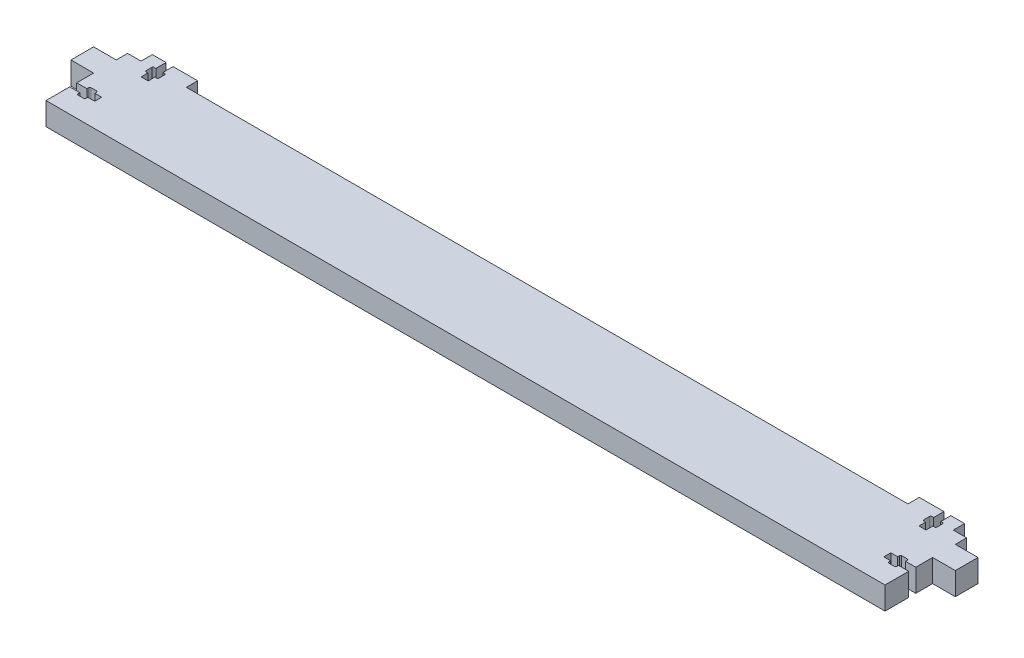
SolidWorks part; units mm, degrees
ref_plane "Front Plane" through (0, 0, 0) normal (0, 0, 1) x (1, 0, 0)
ref_plane "Top Plane" through (0, 0, 0) normal (0, 1, 0) x (1, 0, 0)
ref_plane "Right Plane" through (0, 0, 0) normal (1, 0, 0) x (0, 0, -1)
sketch "Sketch1" plane through (0, 0, 0) normal (0, 1, 0) x (1, 0, 0)
  line L0 (0, 18) -> (0, -18) construction
  line L1 (-185, 18) -> (0, 18)
  line L2 (-185, 18) -> (-185, 13)
  line L3 (-185, -18) -> (0, -18)
  line L4 (0, 18) -> (0, -18)
  line L5 (-185, 18) -> (0, 0) construction
  line L6 (-185, -18) -> (0, 0) construction
  line L7 (-185, 13) -> (-195, 13)
  line L8 (-195, 13) -> (-195, 3)
  line L9 (-195, 3) -> (-185, 3)
  line L10 (-185, 3) -> (-185, -18)
  point P0 (0, 0)
  dimension "D6" = 10
  dimension "D7" = 10
  dimension "D1" = 185
  dimension "D2" = 36
  dimension "D4" = 5
  dimension "D9" = 18
extrude "MainShape" add sketch "Sketch1" along normal blind 10 contours L2 L7 L8 L9 region at (-93.9423, 0, -0.1183)
sketch "Sketch15" plane through (0, 10, 0) normal (0, 1, 0) x (1, 0, 0)
  line L0 (-185, 18) -> (0, 18) construction
  line L1 (-159.1, 23) -> (-179.1, 23)
  line L2 (-159.1, 23) -> (-159.1, 13)
  line L3 (-159.1, 13) -> (-179.1, 13)
  line L4 (-179.1, 23) -> (-179.1, 13)
  line L5 (-159.1, 23) -> (-179.1, 13) construction
  line L6 (-159.1, 13) -> (-179.1, 23) construction
  line L7 (-185, 18) -> (-185, 13) construction
  point P0 (-169.1, 18)
  dimension "D1" = 20
  dimension "D2" = 5
  dimension "D3" = 15.9
extrude "Boss-Extrude4" add sketch "Sketch15" against normal through all
sketch "Sketch2" plane through (0, 10, 0) normal (0, 1, 0) x (1, 0, 0)
  line L0 (-171.5, 23) -> (-171.5, 12) construction
  line L2 (-173.05, 23) -> (-173.05, 18.5)
  line L3 (-173.05, 18.5) -> (-173.85, 18.5)
  line L4 (-174.35, 18) -> (-174.35, 15.5)
  line L5 (-173.85, 15) -> (-173.05, 15)
  line L6 (-173.05, 15) -> (-173.05, 12)
  line L7 (-173.05, 12) -> (-169.95, 12)
  line L8 (-185, 18) -> (-185, 13) construction
  line L9 (-173.05, 23) -> (-169.95, 23)
  line L10 (-169.95, 15) -> (-169.95, 12)
  line L11 (-169.15, 15) -> (-169.95, 15)
  line L12 (-168.65, 18) -> (-168.65, 15.5)
  line L13 (-169.95, 18.5) -> (-169.15, 18.5)
  line L14 (-169.95, 23) -> (-169.95, 18.5)
  line L16 (-185, -6) -> (-174, -6) construction
  line L17 (-159.1, 23) -> (-179.1, 23) construction
  line L50 (-185, 3) -> (-185, -18) construction
  line L51 (-174, -7.55) -> (-174, -4.45)
  line L52 (-174, -4.45) -> (-177, -4.45)
  line L53 (-177, -4.45) -> (-177, -3.65)
  line L54 (-177.5, -3.15) -> (-180, -3.15)
  line L55 (-180.5, -3.65) -> (-180.5, -4.45)
  line L56 (-180.5, -4.45) -> (-185, -4.45)
  line L57 (-185, -4.45) -> (-185, -7.55)
  line L58 (-195, 13) -> (-195, 3) construction
  line L59 (-180.5, -7.55) -> (-185, -7.55)
  line L60 (-180.5, -8.35) -> (-180.5, -7.55)
  line L61 (-177.5, -8.85) -> (-180, -8.85)
  line L62 (-177, -7.55) -> (-177, -8.35)
  line L63 (-174, -7.55) -> (-177, -7.55)
  arc A0 (-174.35, 15.5) -> (-173.85, 15) centre (-173.85, 15.5) ccw
  arc A1 (-173.85, 18.5) -> (-174.35, 18) centre (-173.85, 18) ccw
  arc A2 (-169.15, 18.5) -> (-168.65, 18) centre (-169.15, 18) cw
  arc A3 (-168.65, 15.5) -> (-169.15, 15) centre (-169.15, 15.5) cw
  arc A16 (-177, -3.65) -> (-177.5, -3.15) centre (-177.5, -3.65) ccw
  arc A17 (-180, -3.15) -> (-180.5, -3.65) centre (-180, -3.65) ccw
  arc A18 (-180, -8.85) -> (-180.5, -8.35) centre (-180, -8.35) cw
  arc A19 (-177, -8.35) -> (-177.5, -8.85) centre (-177.5, -8.35) cw
  point P14 (-174.35, 15)
  point P17 (-174.35, 18.5)
  point P28 (-168.65, 18.5)
  point P29 (-168.65, 15)
  point P34 (-195, 8)
  point P45 (-177, -3.15)
  point P48 (-180.5, -3.15)
  dimension "D8" = 0.5
  dimension "D16" = 0.5
  dimension "D1" = 11
  dimension "D2" = 1.55
  dimension "D3" = 1.55
  dimension "D5" = 2.85
  dimension "D6" = 3.5
  dimension "D7" = 13.5
  dimension "D9" = 11
  dimension "D10" = 8
  dimension "D11" = 3.5
  dimension "D12" = 2.85
  dimension "D13" = 1.55
  dimension "D14" = 1.55
  dimension "D15" = 14
  dimension "D4" = 8
extrude "ScrewSlots" cut sketch "Sketch2" against normal through all
mirror "Mirror1" about plane through (0, 0, 0) normal (1, 0, 0) of "Boss-Extrude4", "ScrewSlots", "MainShape"
sketch "Sketch6" [suppressed] plane through (0, 10, 0) normal (0, 1, 0) x (1, 0, 0)
  line L0 (0, -18) -> (0, -48) construction
  line L2 (-185, -18) -> (185, -18) construction
  line L3 (90, -48) -> (-90, -48)
  line L4 (-90, -48) -> (-120, -18)
  line L5 (90, -48) -> (120, -18)
  line L6 (-120, -18) -> (120, -18)
  dimension "D1" = 135
  dimension "D2" = 30
  dimension "D3" = 90
extrude "Boss-Extrude1" [suppressed] add sketch "Sketch6" against normal through all
sketch "Sketch8" [suppressed] plane through (0, 10, 0) normal (0, 1, 0) x (1, 0, 0)
  line L0 (-71.5, 4.8833) -> (-77.5, 4.8833) construction
  line L1 (-77, -1.6167) -> (-72, -1.6167)
  line L2 (-78, -0.6167) -> (-78, 4.3833)
  line L3 (-77, 5.3833) -> (-72, 5.3833)
  line L4 (-71, -0.6167) -> (-71, 4.3833)
  line L5 (-78, -1.6167) -> (-71, 5.3833) construction
  line L6 (-78, 5.3833) -> (-71, -1.6167) construction
  line L7 (-71.5, -1.1167) -> (-71.5, 4.8833) construction
  circle A0 centre (-74.5, -34.7667) radius 6.5
  circle A1 centre (-74.5, -15.8167) radius 5.5
  arc A2 (-77, -1.6167) -> (-78, -0.6167) centre (-77, -0.6167) cw
  circle A3 centre (-74.5, -34.7667) radius 6 construction
  circle A4 centre (-74.5, -15.8167) radius 3.5 construction
  arc A5 (-72, -1.6167) -> (-71, -0.6167) centre (-72, -0.6167) ccw
  arc A6 (-72, 5.3833) -> (-71, 4.3833) centre (-72, 4.3833) cw
  arc A7 (-78, 4.3833) -> (-77, 5.3833) centre (-77, 4.3833) cw
  point P6 (-74.5, 1.8833)
  dimension "D1" = 0.5
  dimension "D2" = 2
  dimension "D3" = 0.5
  dimension "D5" = 1
  dimension "D4" = 0.5
extrude "Cut-Extrude2" [suppressed] cut sketch "Sketch8" against normal through all
sketch "Sketch7" [suppressed] plane through (0, 10, 0) normal (0, 1, 0) x (1, 0, 0)
  circle A0 centre (60.5, -43.0167) radius 1.45
  circle A1 centre (-84.5, -43.0167) radius 1.45
  circle A2 centre (-84.5, 6.4833) radius 1.45
  circle A3 centre (60.5, 6.4833) radius 1.45
  dimension "D1" = 2.9
  dimension "D2" = 2.9
  dimension "D3" = 2.9
  dimension "D4" = 2.9
extrude "Cut-Extrude1" [suppressed] cut sketch "Sketch7" against normal through all
sketch "Sketch9" [suppressed] plane through (0, 10, 0) normal (0, 1, 0) x (1, 0, 0)
  line L0 (0, 7.2333) -> (0, -32.7667) construction
  line L1 (48.5, 7.2333) -> (-48.5, 7.2333) construction
  line L2 (-48.5, -32.7667) -> (48.5, -32.7667) construction
  line L3 (-48.5, -12.7667) -> (48.5, -12.7667) construction
  line L4 (-48.5, 7.2333) -> (-48.5, -32.7667) construction
  line L5 (48.5, -32.7667) -> (48.5, 7.2333) construction
  line L7 (-49, -33.2667) -> (49, -33.2667)
  line L8 (-49, -33.2667) -> (-49, 7.7333)
  line L9 (-49, 7.7333) -> (49, 7.7333)
  line L10 (49, -33.2667) -> (49, 7.7333)
  line L11 (-49, -33.2667) -> (49, 7.7333) construction
  line L12 (-49, 7.7333) -> (49, -33.2667) construction
  point P12 (0, -12.7667)
  dimension "D1" = 0.5
  dimension "D2" = 0.5
extrude "Cut-Extrude3" [suppressed] cut sketch "Sketch9" against normal through all and the other way through all
sketch "Sketch10" [suppressed] plane through (0, 10, 0) normal (0, 1, 0) x (1, 0, 0)
  line L0 (20, -39.2667) -> (20, -40.7667) construction
  line L1 (40, -39.2667) -> (0, -39.2667) construction
  line L2 (0, -40.7667) -> (40, -40.7667) construction
  line L3 (0, -40.0167) -> (40, -40.0167) construction
  line L4 (0, -39.2667) -> (0, -40.7667) construction
  line L5 (40, -40.7667) -> (40, -39.2667) construction
  line L7 (-0.2, -40.9667) -> (40.2, -40.9667)
  line L8 (-0.2, -40.9667) -> (-0.2, -39.0667)
  line L9 (-0.2, -39.0667) -> (40.2, -39.0667)
  line L10 (40.2, -40.9667) -> (40.2, -39.0667)
  line L11 (-0.2, -40.9667) -> (40.2, -39.0667) construction
  line L12 (-0.2, -39.0667) -> (40.2, -40.9667) construction
  point P12 (20, -40.0167)
  dimension "D1" = 0.2
  dimension "D2" = 0.2
extrude "Cut-Extrude4" [suppressed] cut sketch "Sketch10" against normal through all
sketch "Sketch12" [suppressed] plane through (0, 0, 0) normal (0, -1, 0) x (-1, 0, 0)
  line L1 (81.4, -9.8167) -> (67.6, -9.8167)
  line L2 (81.4, -9.8167) -> (81.4, -21.8167)
  line L3 (81.4, -21.8167) -> (67.6, -21.8167)
  line L4 (67.6, -9.8167) -> (67.6, -21.8167)
  line L5 (81.4, -9.8167) -> (67.6, -21.8167) construction
  line L6 (81.4, -21.8167) -> (67.6, -9.8167) construction
  point P0 (74.5, -15.8167)
  dimension "D1" = 13.8
  dimension "D2" = 12
extrude "PotentiometerAdjustment" [suppressed] cut sketch "Sketch12" against normal through all
sketch "Sketch11" [suppressed] plane through (0, 0, 0) normal (0, -1, 0) x (1, 0, 0)
  line L1 (-139, -7) -> (-167, -7)
  line L2 (-137, -5) -> (-137, 2)
  line L3 (-139, 4) -> (-167, 4)
  line L4 (-169, -5) -> (-169, 2)
  line L5 (-137, -7) -> (-169, 4) construction
  line L6 (-137, 4) -> (-169, -7) construction
  line L7 (173.05, -12) -> (169.95, -12) construction
  line L8 (-174, 7.55) -> (-174, 4.45) construction
  arc A0 (-137, 2) -> (-139, 4) centre (-139, 2) ccw
  arc A1 (-167, 4) -> (-169, 2) centre (-167, 2) ccw
  arc A2 (-167, -7) -> (-169, -5) centre (-167, -5) cw
  arc A3 (-139, -7) -> (-137, -5) centre (-139, -5) ccw
  point P0 (-153, -1.5)
  dimension "D3" = 2
  dimension "D1" = 32
  dimension "D2" = 11
  dimension "D4" = 5
  dimension "D5" = 5
extrude "LCDCableCutout" [suppressed] cut sketch "Sketch11" against normal through all
sketch "Sketch13" plane through (0, 10, 0) normal (0, 1, 0) x (1, 0, 0)
  line L0 (0, 18) -> (0, -18) construction
  line L1 (-169.95, 18) -> (169.95, 18) construction
  line L2 (-185, -18) -> (185, -18) construction
  line L3 (120, 18) -> (-120, 18) construction
  line L4 (120, 8) -> (-120, 8)
  line L5 (120, 28) -> (-120, 28)
  arc A0 (120, 8) -> (120, 28) centre (120, 18) ccw
  arc A1 (-120, 28) -> (-120, 8) centre (-120, 18) ccw
  point P8 (0, 18)
  dimension "D2" = 120
  dimension "D1" = 10
extrude "Cut-Extrude5" [suppressed] cut sketch "Sketch13" against normal through all
sketch "Sketch14" [suppressed] plane through (0, 10, 0) normal (0, 1, 0) x (1, 0, 0)
  line L1 (-169.95, 18) -> (169.95, 18) construction
  line L3 (-156.5, 18) -> (-156.5, 28) construction
  line L4 (-161.5, 18) -> (-151.5, 18)
  line L5 (-161.5, 18) -> (-161.5, 28)
  line L6 (-161.5, 28) -> (-151.5, 28)
  line L7 (-151.5, 18) -> (-151.5, 28)
  line L8 (-173.05, 12) -> (-169.95, 12) construction
  line L9 (154, 18) -> (154, 28) construction
  line L10 (149, 18) -> (149, 28)
  line L11 (159, 28) -> (149, 28)
  line L12 (159, 18) -> (159, 28)
  line L13 (159, 18) -> (149, 18)
  point P12 (-171.5, 12)
  dimension "D1" = 10
  dimension "D2" = 10
  dimension "D3" = 15
extrude "Boss-Extrude3" [suppressed] add sketch "Sketch14" against normal through all
equation "\"Y-ROD-SPACING\"=75"
equation "\"Y-BED-OFFSET\"=2"
equation "\"Y-BED-ROD-INSET\"=3.5"
equation "\"T-SLOT-NUT-FILLET-RADIUS\"=0.5"
equation "\"T-SLOT-SCREW-SHAFT-RADIUS\"=1.55"
equation "\"T-SLOT-SCREW-SHAFT-CUTOUT-LENGTH\"=11"
equation "\"T-SLOT-NUT-DEPTH\"=3.5"
equation "\"T-SLOT-NUT-WIDTH\"=2.85"
equation "\"T-SLOT-NUT-END-DISTANCE\"=8"
equation "\"ACRYLIC-TAB-CUTOUT-SIZE\"=\"ACRYLIC-THICKNESS\"+\"ACRYLIC-TAB-TOLERANCE\"*2"
equation "\"ACRYLIC-M3-HOLE\"=2.9"
equation "\"SMOOTHROD-CAP-SCREW-DISTANCE\"=20"
equation "\"D2@Sketch2\"=\"T-SLOT-SCREW-SHAFT-RADIUS\""
equation "\"D1@Sketch2\"=\"T-SLOT-SCREW-SHAFT-CUTOUT-LENGTH\""
equation "\"D6@Sketch2\"=\"T-SLOT-NUT-DEPTH\""
equation "\"D5@Sketch2\"=\"T-SLOT-NUT-WIDTH\""
equation "\"D3@Sketch2\"=\"T-SLOT-SCREW-SHAFT-RADIUS\""
equation "\"D8@Sketch2\"=\"T-SLOT-NUT-FILLET-RADIUS\""
equation "\"D4@Sketch2\"=\"T-SLOT-NUT-END-DISTANCE\""
equation "\"D11@Sketch2\"=\"T-SLOT-NUT-DEPTH\""
equation "\"D10@Sketch2\"=\"T-SLOT-NUT-END-DISTANCE\""
equation "\"D13@Sketch2\"=\"T-SLOT-SCREW-SHAFT-RADIUS\""
equation "\"D14@Sketch2\"=\"T-SLOT-SCREW-SHAFT-RADIUS\""
equation "\"D16@Sketch2\"=\"T-SLOT-NUT-FILLET-RADIUS\""
equation "\"D9@Sketch2\"=\"T-SLOT-SCREW-SHAFT-CUTOUT-LENGTH\""
equation "\"ACRYLIC-TAB-WIDTH\"=\"ACRYLIC-THICKNESS\""
equation "\"D6@Sketch1\"=\"ACRYLIC-TAB-WIDTH\""
equation "\"D7@Sketch1\"=\"ACRYLIC-TAB-WIDTH\""
equation "\"FRAME-WIDTH-INNER\"=370"
equation "\"D1@Sketch1\"=\"FRAME-WIDTH-INNER\"/2"
equation "\"X-ROD-SPACING\"=45"
equation "\"Z-ROD-SPACING\"=17.5"
equation "\"ACRYLIC-THICKNESS\"=10"
equation "\"ACRYLIC-THICKNESS2\"=4.5"
equation "\"NEMA17-HOLE-SPACING\"=31"
equation "\"NEMA17-CENTRAL-CUTOUT\"=22.5"
equation "\"Z-BRACKET-REACH\"=57"
equation "\"TOP-BRACKET-SPACING\"=40"
equation "\"SMOOTHROD-X-LENGTH\"=350"
equation "\"SMOOTHROD-Y-LENGTH\"=350"
equation "\"SMOOTHROD-Z-LENGTH\"=350"
equation "\"SMOOTHROD-TIGHTENING-HEADROOM\"=.25"
equation "\"LEADSCREW-Z-LENGTH\"=300"
equation "\"SCREW-LENGTH-FRAME\"=\"ACRYLIC-THICKNESS\" + 10"
equation "\"SCREW-HEAD-RADIUS\"=6"
equation "\"PRINTED-X-SMOOTHROD-DIAMETER\"=8.8"
equation "\"PRINTED-X-SMOOTHROD-CUTOUT\"=10"
equation "\"PRINTED-X-BASE-HEIGHT\"=10"
equation "\"PRINTED-LM8UU-CUTOUT-SIZE\"=15.5"
equation "\"PRINTED-LM8UU-CUTOUT-LENGTH\"=24.5"
equation "\"PRINTED-X-IDLER-HEIGHT\"=16"
equation "\"PSU-MOUNTING-WIDTH\"=95"
equation "\"PSU-MOUNTING-HEIGHT\"=177"
equation "\"D1@MainShape\"=\"ACRYLIC-THICKNESS\""
equation "\"Y-BELT-TO-ROD-DISTANCE\"=20"
equation "\"SPOOL-HOLDER-ROD-SPACING\"=150"
equation "\"Z-ROD-INSET\"=13.5"
equation "\"D7@Sketch2\"=\"Z-ROD-INSET\""
equation "\"D1@Sketch7\"=\"ACRYLIC-M3-HOLE\""
equation "\"D2@Sketch7\"=\"ACRYLIC-M3-HOLE\""
equation "\"D3@Sketch7\"=\"ACRYLIC-M3-HOLE\""
equation "\"D4@Sketch7\"=\"ACRYLIC-M3-HOLE\""
equation "\"Y-BED-SCREW-SPACING\"=209"
equation "\"Y-BED-SCREW-CUTOUT-SLOT-HEIGHT\"=2.5"
equation "\"ACRYLIC-TAB-TOLERANCE\"=-.05"
equation "\"SCREW-LENGTH-MOTOR\"=\"ACRYLIC-THICKNESS\" + 5"
equation "\"SCREW-LENGTH-EXTRUDER\"=28"
equation "\"PRINTED-M3-HOLE\"=3.5"
equation "\"PRINTED-M3-NUT-AF\"=6.25"
equation "\"ACRYLIC-X-CARRIAGE-WIDTH\"=55"
equation "\"ACRYLIC-X-CARRIAGE-HEIGHT\"=75"
equation "\"ACRYLIC-X-CARRIAGE-LM8UU-CUTOUT-WIDTH\"=24.25"
equation "\"ACRYLIC-X-CARRIAGE-LM8UU-CUTOUT-HEIGHT\"=11.0"
equation "\"ACRYLIC-X-CARRIAGE-SCREW-SPACING-X\"=15"
equation "\"ACRYLIC-X-CARRIAGE-SCREW-SPACING-Y\"=33"
equation "\"ACRYLIC-X-CARRIAGE-CENTER-TAB-SPACING\"=14"
equation "\"ACRYLIC-X-CARRIAGE-EXTRUDER-OFFSET\"=26"
equation "\"ACRYLIC-X-CARRIAGE-EXTRUDER-ANGLE\"=90"
equation "\"ACRYLIC-X-CARRIAGE-EXTRUDER-SHELF-DEPTH\"=\"ACRYLIC-X-CARRIAGE-EXTRUDER-OFFSET\" + 28"
equation "\"ACRYLIC-X-CARRIAGE-EXTRUDER-BRACE-SPACING\"=23"
equation "\"ACRYLIC-X-CARRIAGE-EXTRUDER-BRACE-TAB-OFFSET\"=20"
equation "\"ACRYLIC-X-CARRIAGE-EXTRUDER-BRACE-HEIGHT\"=35"
equation "\"ACRYLIC-X-CARRIAGE-EXTRUDER-BRACE-SCREW-SPACING\"=22"
equation "\"ACRYLIC-X-CARRIAGE-DUAL-WIDTH-MULTIPLIER\"=1.65"
equation "\"ACRYLIC-X-CARRIAGE-DUAL-HOTEND-SPACING\"=42"
equation "\"ACRYLIC-X-CARRIAGE-DUAL-WIDTH\"=75"
equation "\"ACRYLIC-X-CARRIAGE-DUAL-HOTEND-SEPARATION\"=36"
equation "\"ACRYLIC-X-CARRIAGE-DUAL-MOUNT-PLATE-DEPTH\"=75"
equation "\"ACRYLIC-X-CARRIAGE-DUAL-MOUNT-BRACE-WIDTH\"=33"
equation "\"ACRYLIC-X-CARRIAGE-DUAL-MOUNT-SCREW-WIDTH\"=40"
equation "\"BLOWER-FAN-WIDTH\"=15"
equation "\"D1@Sketch14\"=\"ACRYLIC-TAB-WIDTH\""
equation "\"D2@Sketch14\"=\"ACRYLIC-THICKNESS\""
equation "\"D3@Sketch15\"=\"Z-ROD-INSET\"+2.4"
equation "\"D12@Sketch2\"=\"T-SLOT-NUT-WIDTH\""
